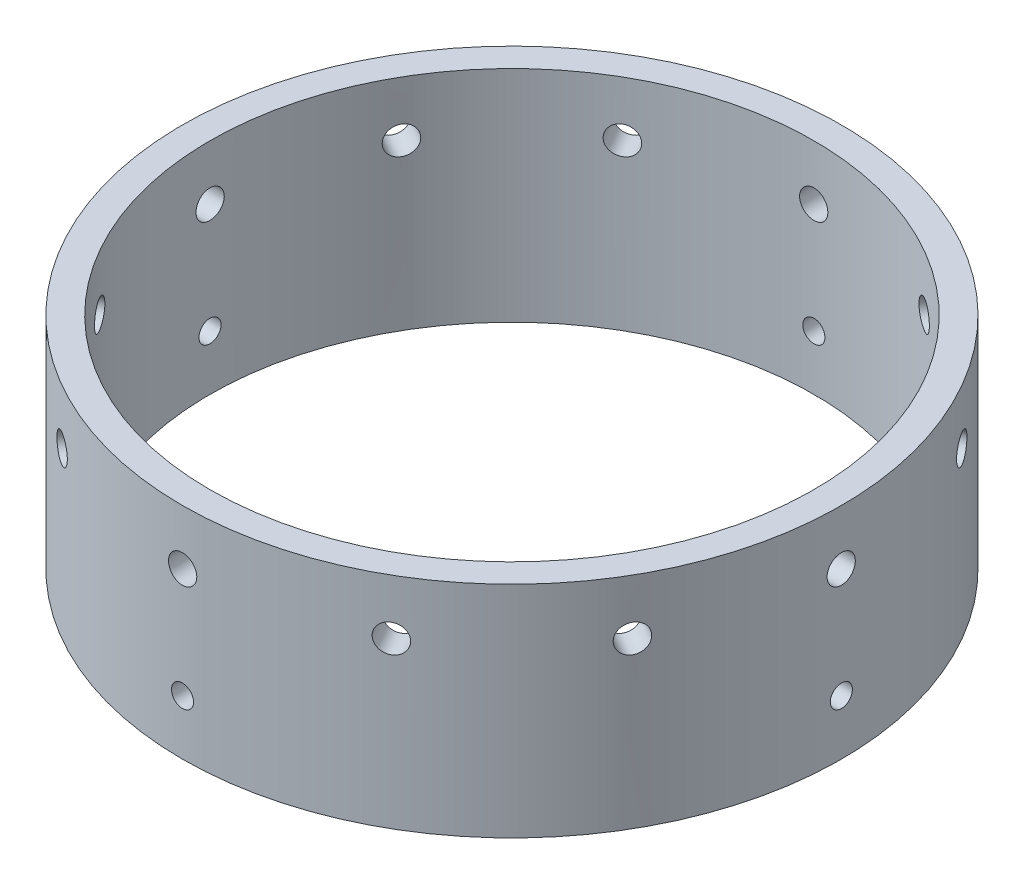
SolidWorks part; units mm, degrees
ref_plane "Front Plane" through (0, 0, 0) normal (0, 0, 1) x (1, 0, 0)
ref_plane "Top Plane" through (0, 0, 0) normal (0, 1, 0) x (1, 0, 0)
ref_plane "Right Plane" through (0, 0, 0) normal (1, 0, 0) x (0, 0, -1)
sketch "Sketch2" plane through (0, 0, 0) normal (0, 1, 0) x (1, 0, 0)
  circle A0 centre (0, 0) radius 76.2
  circle A1 centre (0, 0) radius 69.85
  dimension "D1" = 139.7
  dimension "D2" = 152.4
extrude "Boss-Extrude1" add sketch "Sketch2" along normal blind 50.8
sketch "Sketch3" plane through (0, 0, 0) normal (0, 0, 1) x (1, 0, 0)
  line L0 (-76.2, 0) -> (76.2, 0) construction
  line L1 (76.2, 50.8) -> (-76.2, 50.8) construction
  line L2 (76.2, 50.8) -> (-76.2, 50.8) construction
  line L3 (-76.2, 0) -> (76.2, 0) construction
  line L4 (0, 25.4) -> (0, 50.8) construction
  line L7 (-76.2, 25.4) -> (76.2, 25.4) construction
  line L8 (-76.2, 50.8) -> (-76.2, 0) construction
  line L9 (76.2, 0) -> (76.2, 50.8) construction
  line L11 (0, 0) -> (0, 25.4) construction
  circle A0 centre (0, 12.7) radius 3.2639
  circle A1 centre (0, 38.1) radius 3.2639
  dimension "D2" = 6.5278
  dimension "D1" = 6.5278
  dimension "D3" = 12.7
  dimension "D4" = 12.7
extrude "Cut-Extrude1" cut sketch "Sketch3" against normal through all contours A1
pattern_circular "CirPattern1" count 12 over 360 about axis through (0, 50.8, 0) along (0, 1, 0) of "Cut-Extrude1"
ref_plane "Plane1" through (0, 0, 76.2) normal (0, 0, 1) x (1, 0, 0)
sketch "Sketch7" plane through (0, 0, 76.2) normal (0, 0, 1) x (1, 0, 0)
  circle A1 centre (0, 38.1) radius 3.2639
  circle A2 centre (0, 38.1) radius 3.2639 construction
  circle A3 centre (0, 12.7) radius 3.2639
  circle A4 centre (0, 12.7) radius 3.2639 construction
  point P0 (0, 12.7)
  dimension "D1" = 0
  dimension "D2" = 0
hole_wizard "1/4-20 Tapped Hole2" positions "Sketch7" profile "Sketch8" tap size "1/4-20" standard "ANSI Inch" end condition up to next
sketch "Sketch8" plane through (0, 12.7, 76.2) normal (1, 0, 0) x (0, -1, 0)
  line L0 (0, 0) -> (0, 6.35)
  line L1 (0, 6.35) -> (2.5527, 6.35)
  line L2 (2.5527, 6.35) -> (2.5527, 0)
  line L5 (2.5527, 0) -> (0, 0)
  line L11 (0, -6.35) -> (0, 107.95) construction
  dimension "Thru Tap Drill Dia." = 5.1054
  dimension "Thru Tap Drill Depth" = 6.35
cosmetic thread "Hole Thread2" parameters "D2"=6.35
pattern_circular "CirPattern3" count 4 over 360 about axis through (0, 50.8, 0) along (0, 1, 0) of "1/4-20 Tapped Hole2"
cosmetic thread "Hole Thread3" parameters "D2"=6.35
cosmetic thread "Hole Thread4" parameters "D2"=6.35
cosmetic thread "Hole Thread5" parameters "D2"=6.35
